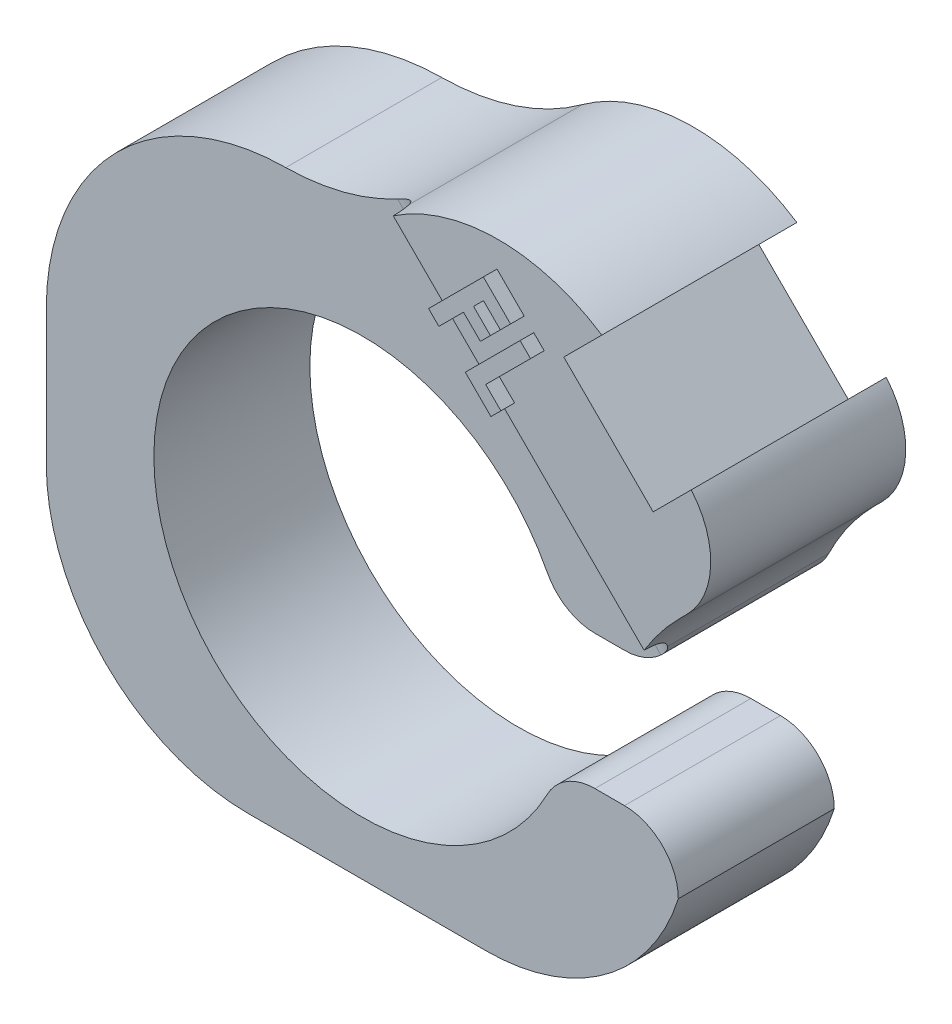
SolidWorks part; units mm, degrees
ref_plane "Front Plane" through (0, 0, 0) normal (0, 0, 1) x (1, 0, 0)
ref_plane "Top Plane" through (0, 0, 0) normal (0, 1, 0) x (1, 0, 0)
ref_plane "Right Plane" through (0, 0, 0) normal (1, 0, 0) x (0, 0, -1)
sketch "Sketch1" plane through (0, 0, 0) normal (0, 0, 1) x (1, 0, 0)
  line L0 (0, 9.25) -> (0, -12.25) construction
  line L2 (-11.75, 9.25) -> (-11.75, -10.25)
  line L3 (-9.75, -12.25) -> (9.75, -12.25)
  line L4 (11.75, 9.25) -> (11.75, 2)
  line L8 (0, -2.5) -> (11.75, -2.5) construction
  line L10 (-11.75, -10.25) -> (-11.75, -12.25)
  line L11 (-11.75, -12.25) -> (-9.75, -12.25)
  line L14 (11.75, 0) -> (13.7578, 0) construction
  line L15 (9.75, 0) -> (8.6494, 0)
  line L16 (9.75, -5) -> (8.6494, -5)
  line L17 (11.75, -7) -> (11.75, -10.25)
  line L20 (11.75, -10.25) -> (11.75, -12.25)
  line L21 (11.75, -12.25) -> (9.75, -12.25)
  line L25 (-11.75, 9.25) -> (11.75, 9.25)
  arc A0 (6.8752, 1.0769) -> (6.8752, -6.0769) centre (0, -2.5) ccw
  arc A1 (6.8752, 1.0769) -> (8.6494, 0) centre (8.6494, 2) ccw
  arc A2 (6.8752, -6.0769) -> (8.6494, -5) centre (8.6494, -7) cw
  arc A3 (9.75, -5) -> (11.75, -7) centre (9.75, -7) cw
  arc A4 (11.75, 2) -> (9.75, 0) centre (9.75, 2) cw
  point P0 (0, 0)
  point P27 (11.75, -5)
  point P45 (0, 10.25)
  dimension "D6" = 15.5
  dimension "D8" = 2
  dimension "D4" = 11.75
  dimension "D7" = 2.5
extrude "Boss-Extrude1" add sketch "Sketch1" along normal blind 5.8
sketch "Sketch3" plane through (0, 0, 5.8) normal (0, 0, 1) x (1, 0, 0)
  line L0 (-1.4053, 7.0549) -> (6.5407, 15.0009)
  line L2 (6.5407, 15.0009) -> (17.5009, 4.0407)
  line L4 (12.0208, 9.5208) -> (0, -2.5) construction
  line L5 (0.1768, 8.6369) -> (11.1369, -2.3232) construction
  line L6 (17.5009, 4.0407) -> (11.75, 2)
  line L7 (11.75, 2) -> (-1.4053, 7.0549)
  point P1 (5.6569, 3.1569)
  dimension "D1" = 17
extrude "Boss-Extrude2" add sketch "Sketch3" against normal blind 5.8 contours L7 L0 L2 L6
sketch "Sketch5" plane through (0, 0, 5.8) normal (0, 0, 1) x (1, 0, 0)
  line L0 (11.75, 2) -> (2.6449, 11.1051)
  line L1 (-1.4053, 7.0549) -> (6.5407, 15.0009) construction
  line L3 (2.6449, 11.1051) -> (6.5407, 15.0009)
  line L4 (6.5407, 15.0009) -> (17.5009, 4.0407)
  line L5 (17.5009, 4.0407) -> (11.75, 2)
extrude "Boss-Extrude3" add sketch "Sketch5" along normal blind 4.5
sketch "Sketch6" plane through (0, 0, 5.8) normal (0, 0, 1) x (1, 0, 0)
  line L0 (8.9449, 9.7683) -> (10.3591, 11.1825)
  line L1 (8.9449, 9.7683) -> (12.2683, 6.4449)
  line L2 (10.3591, 11.1825) -> (13.6825, 7.8591)
  line L3 (12.2683, 6.4449) -> (13.6825, 7.8591)
  line L4 (12.0208, 9.5208) -> (10.6066, 8.1066) construction
  line L5 (9.652, 10.4754) -> (12.9754, 7.152) construction
  line L6 (6.5407, 15.0009) -> (17.5009, 4.0407) construction
  point P1 (11.3137, 8.8137)
  dimension "D1" = 2
  dimension "D2" = 4.7
extrude "Cut-Extrude2" cut sketch "Sketch6" against normal through all both and the other way through all
fillet "Fillet6" radius 9 1 edges at (-11.75, 9.25, 2.9)
fillet "Fillet7" radius 7.5 1 edges at (-11.75, -12.25, 2.9)
fillet "Fillet8" radius 7.5 1 edges at (11.75, -12.25, 2.9)
fillet "Fillet14" radius 9 1 edges at (0.7898, 9.25, 2.9)
fillet "Fillet15" radius 7 1 edges at (6.5407, 15.0009, 5.15)
sketch "Sketch9" plane through (0, 0, 5.8) normal (0, 0, 1) x (1, 0, 0)
  line L0 (11.75, 2) -> (16.3624, 6.6124)
  line L1 (6.5407, 15.0009) -> (17.5009, 4.0407) construction
  line L2 (16.3624, 6.6124) -> (17.5009, 4.0407)
  line L3 (17.5009, 4.0407) -> (11.75, 2)
extrude "Cut-Extrude4" cut sketch "Sketch9" against normal through all both and the other way through all
fillet "Fillet19" radius 3 1 edges at (15.6458, 5.8958, 5.15)
fillet "Fillet21" radius 1.5 1 edges
fillet "Fillet22" radius 9 1 edges at (11.75, 2, 3.65)
sketch "Sketch10" plane through (0, 0, 10.3) normal (0, 0, 1) x (1, 0, 0)
  line L1 (0, 20.571) -> (20.3334, 20.571)
  line L2 (0, 20.571) -> (0, -4.7113)
  line L3 (0, -4.7113) -> (20.3334, -4.7113)
  line L4 (20.3334, 20.571) -> (20.3334, -4.7113)
extrude "Cut-Extrude5" cut sketch "Sketch10" against normal blind 3.048
sketch "Sketch13" plane through (0, 0, 7.252) normal (0, 0, 1) x (1, 0, 0)
  text T0 "  FL" font "Century Gothic" height in points 11
extrude "Boss-Extrude4" add sketch "Sketch13" along normal blind 0.508
